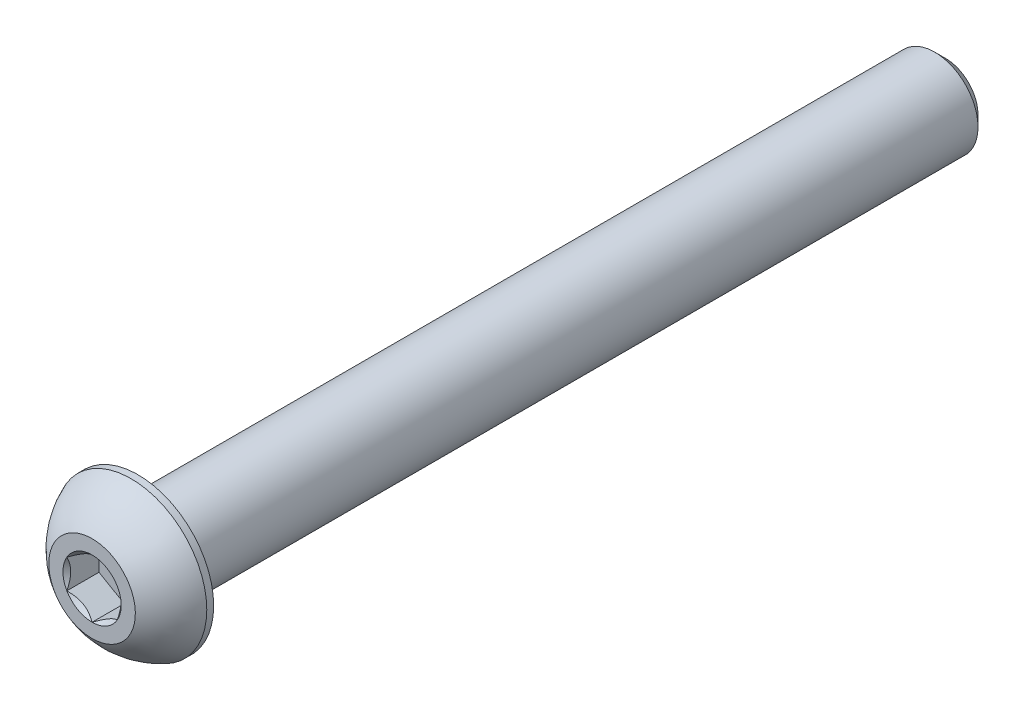
SolidWorks part; units mm, degrees
ref_plane "Front" through (0, 0, 0) normal (0, 0, 1) x (1, 0, 0)
ref_plane "Top" through (0, 0, 0) normal (0, 1, 0) x (1, 0, 0)
ref_plane "Right" through (0, 0, 0) normal (1, 0, 0) x (0, 0, -1)
sketch "Sketch1" plane through (0, 0, 0) normal (1, 0, 0) x (0, 0, -1)
  line L2 (5.0546, 4.7625) -> (93.9546, 4.7625)
  line L3 (93.9546, 4.7625) -> (93.9546, 0)
  line L4 (93.9546, 0) -> (5.0546, 0)
  line L6 (4.2964, 8.3312) -> (5.0546, 8.3312) construction
  line L7 (93.9546, 4.7625) -> (93.9546, -4.7625) construction
  line L8 (0, 0) -> (5.0546, 0) construction
  line L9 (5.0546, 8.3312) -> (5.0546, -8.3312) construction
  line L11 (5.0546, 4.7625) -> (5.0546, 0)
  line L13 (0, 2.7781) -> (0, -2.7781) construction
  line L14 (0, 2.7781) -> (0, 4.7625) construction
  arc A3 (0, 4.7625) -> (4.2964, 8.3312) centre (7.5862, 0) cw construction
  dimension "D1" = 0.7582
revolve "Revolve1" add sketch "Sketch1" angle 360 mid plane about L4
sketch "Sketch3" plane through (0, 0, -93.9546) normal (0, 0, -1) x (-1, 0, 0)
  circle A0 centre (0, 0) radius 4.7625
curve "Helix/Spiral1" pitch 1.5875 height 90.4875 turns 57
sketch "Sketch2" plane through (0, 0, 0) normal (1, 0, 0) x (0, 0, -1)
  line L0 (93.9546, 4.7625) -> (95.3437, 4.7625)
  line L1 (95.3437, 4.7625) -> (94.7484, 3.7314)
  line L2 (94.7484, 3.7314) -> (94.5499, 3.7314)
  line L3 (94.5499, 3.7314) -> (93.9546, 4.7625)
  line L4 (94.2523, 4.2469) -> (95.046, 4.2469) construction
  dimension "D1" = 60
  dimension "D2" = 0.1984
  dimension "D3" = 0.7937
chamfer "Chamfer1" distance 1.1906 angle 45 1 edges at (0, 4.7625, -93.9546)
sweep "Cut-Sweep1" [suppressed] cut profiles "Sketch2" path "Helix/Spiral1"
sketch "Sketch7" plane through (0, 0, 0) normal (1, 0, 0) x (0, 0, -1)
  line L6 (4.2964, 8.3312) -> (5.0546, 8.3312) construction
  line L8 (0, 0) -> (5.0546, 0) construction
  line L11 (5.0546, 8.3312) -> (5.0546, -8.3312) construction
  line L12 (4.2964, 8.3312) -> (5.0546, 8.3312)
  line L13 (0, 0) -> (5.0546, 0)
  line L14 (0, 2.7781) -> (0, -2.7781) construction
  line L15 (5.0546, 8.3312) -> (5.0546, 0)
  line L16 (0, 4.7625) -> (0, 0)
  arc A2 (4.2964, 8.3312) -> (0, 4.7625) centre (7.5862, 0) ccw construction
  arc A3 (4.2964, 8.3312) -> (0, 4.7625) centre (7.5862, 0) ccw
revolve "Revolve2" add sketch "Sketch7" angle 360 mid plane about L13
sketch "Sketch5" plane through (0, 0, 0) normal (0, 0, 1) x (1, 0, 0)
  line L1 (2.7781, -1.604) -> (2.7781, 1.604)
  line L2 (2.7781, 1.604) -> (0, 3.2079)
  line L3 (0, 3.2079) -> (-2.7781, 1.604)
  line L4 (-2.7781, 1.604) -> (-2.7781, -1.604)
  line L5 (-2.7781, -1.604) -> (0, -3.2079)
  line L6 (0, -3.2079) -> (2.7781, -1.604)
  circle A0 centre (0, 0) radius 2.7781 construction
extrude "Cut-Extrude2" cut sketch "Sketch5" against normal blind 3.5382
sketch "Sketch6" plane through (0, 0, 0) normal (0, 0, 1) x (1, 0, 0)
  circle A0 centre (0, 0) radius 3.2079
extrude "Cut-Extrude3" cut sketch "Sketch6" against normal blind 3.5382 draft 45
sketch "Sketch9" [suppressed] plane through (0, 0, -5.0546) normal (0, 0, 1) x (1, 0, 0)
  circle A2 centre (0, 0) radius 4.7625
extrude "Boss-Extrude2" [suppressed] add sketch "Sketch9" against normal offset from surface (12.7 mm away) 28.575
sketch "Sketch10" plane through (0, 0, 0) normal (1, 0, 0) x (0, 0, -1)
  line L0 (93.9546, 4.7625) -> (93.9546, -4.7625) construction
  point P0 (91.5734, -4.7625)
  dimension "D1" = 2.3813
equation "\"D3@Helix/Spiral1\" = \"Lg@Sketch1\" + \"D4@Helix/Spiral1\""
equation "\"D2@Sketch2\" = \"D4@Helix/Spiral1\" * .125"
equation "\"D3@Sketch2\" = \"D4@Helix/Spiral1\" * .5"
equation "\"D1@Chamfer1\" = \"D4@Helix/Spiral1\" * .75"
equation "\"D1@Cut-Extrude2\" = \"Head Ht@Sketch1\" * .7"
equation "\"D1@Sketch1\" = \"Head Ht@Sketch1\" * .15"
equation "\"D1@Sketch10\" = \"D4@Helix/Spiral1\" * 1.5"
equation "\"D1@Cut-Extrude3\" = \"D1@Cut-Extrude2\""
